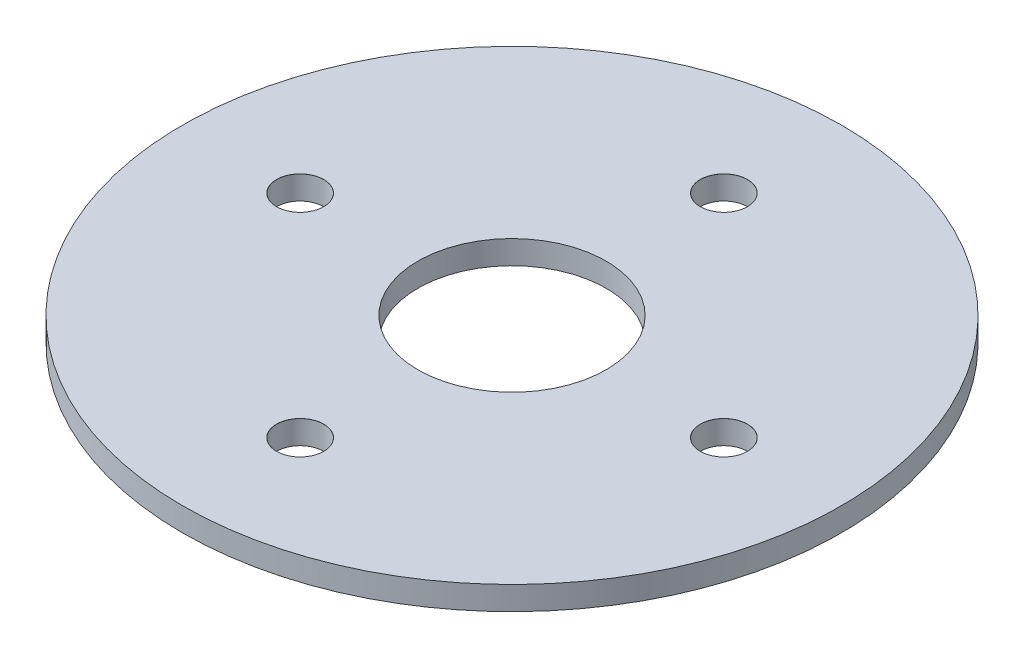
SolidWorks part; units mm, degrees
ref_plane "前视基准面" through (0, 0, 0) normal (0, 0, 1) x (1, 0, 0)
ref_plane "上视基准面" through (0, 0, 0) normal (0, 1, 0) x (1, 0, 0)
ref_plane "右视基准面" through (0, 0, 0) normal (1, 0, 0) x (0, 0, -1)
ref_axis "基准轴1" through (0, 142.6189, 0) along (0, -1, 0)
ref_plane "基准面z0.200" through (0, 0, 200) normal (0, 0, 1) x (1, 0, 0)
ref_plane "基准面z0.140" through (0, 0, 140) normal (0, 0, 1) x (1, 0, 0)
sketch "草图1" plane through (0, 0, 0) normal (0, 1, 0) x (1, 0, 0)
  circle A0 centre (0, 0) radius 140
  circle A1 centre (0, 0) radius 40
  dimension "D1" = 280
  dimension "D2" = 80
extrude "凸台-拉伸1" add sketch "草图1" along normal blind 10
sketch "草图2" plane through (0, 10, 0) normal (0, 1, 0) x (1, 0, 0)
  circle A0 centre (0, 0) radius 90 construction
  point P3 (90, 0)
  point P4 (0, 90)
  point P5 (-90, 0)
  point P6 (0, -90)
  dimension "D1" = 180
hole_wizard "Ø20.0 (20) 直径孔1" positions "草图2" profile "草图3" hole size "Ø20.0" standard "GB" end condition through all
sketch "草图3" plane through (0, 10, 90) normal (1, 0, 0) x (0, 0, 1)
  line L0 (0, 0) -> (0, 10)
  line L1 (0, 10) -> (10, 10)
  line L2 (10, 10) -> (10, 0.025)
  line L3 (10, 0.025) -> (10.025, 0)
  line L5 (10.025, 0) -> (0, 0)
  line L6 (-10, 0.025) -> (-10.025, 0) construction
  line L11 (0, -6.35) -> (0, 107.95) construction
  dimension "通孔孔直径" = 20
  dimension "通孔孔深度" = 10
  dimension "近端锥形沉头孔直径" = 20.05
  dimension "近端锥形沉头孔角度" = 90
